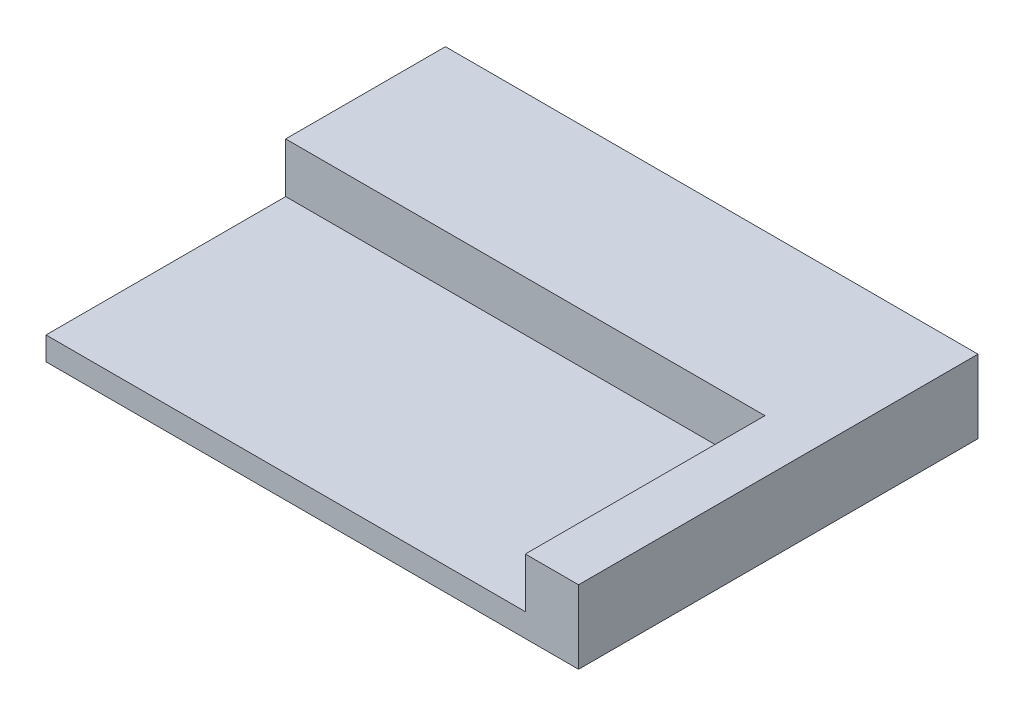
SolidWorks part; units mm, degrees
ref_plane "Front Plane" through (0, 0, 0) normal (0, 0, 1) x (1, 0, 0)
ref_plane "Top Plane" through (0, 0, 0) normal (0, 1, 0) x (1, 0, 0)
ref_plane "Right Plane" through (0, 0, 0) normal (1, 0, 0) x (0, 0, -1)
sketch "Sketch1" plane through (0, 0, 0) normal (0, 1, 0) x (1, 0, 0)
  line L1 (-80, 60) -> (80, 60)
  line L2 (-80, 60) -> (-80, -60)
  line L3 (-80, -60) -> (80, -60)
  line L4 (80, 60) -> (80, -60)
  dimension "D1" = 160
  dimension "D2" = 120
  dimension "D3" = 80
  dimension "D4" = 60
extrude "Boss-Extrude1" add sketch "Sketch1" along normal blind 7
sketch "Sketch2" plane through (0, 7, 0) normal (0, 1, 0) x (1, 0, 0)
  line L0 (-80, 60) -> (-80, 12)
  line L1 (-80, 60) -> (-80, -60) construction
  line L2 (-80, 12) -> (64, 12)
  line L3 (64, 12) -> (64, -60)
  line L4 (-80, -60) -> (80, -60) construction
  line L5 (64, -60) -> (80, -60)
  line L6 (80, -60) -> (80, 60) construction
  line L7 (80, -60) -> (80, 60)
  line L8 (80, 60) -> (-80, 60)
  dimension "D1" = 48
  dimension "D2" = 16
extrude "Boss-Extrude2" add sketch "Sketch2" along normal blind 15
